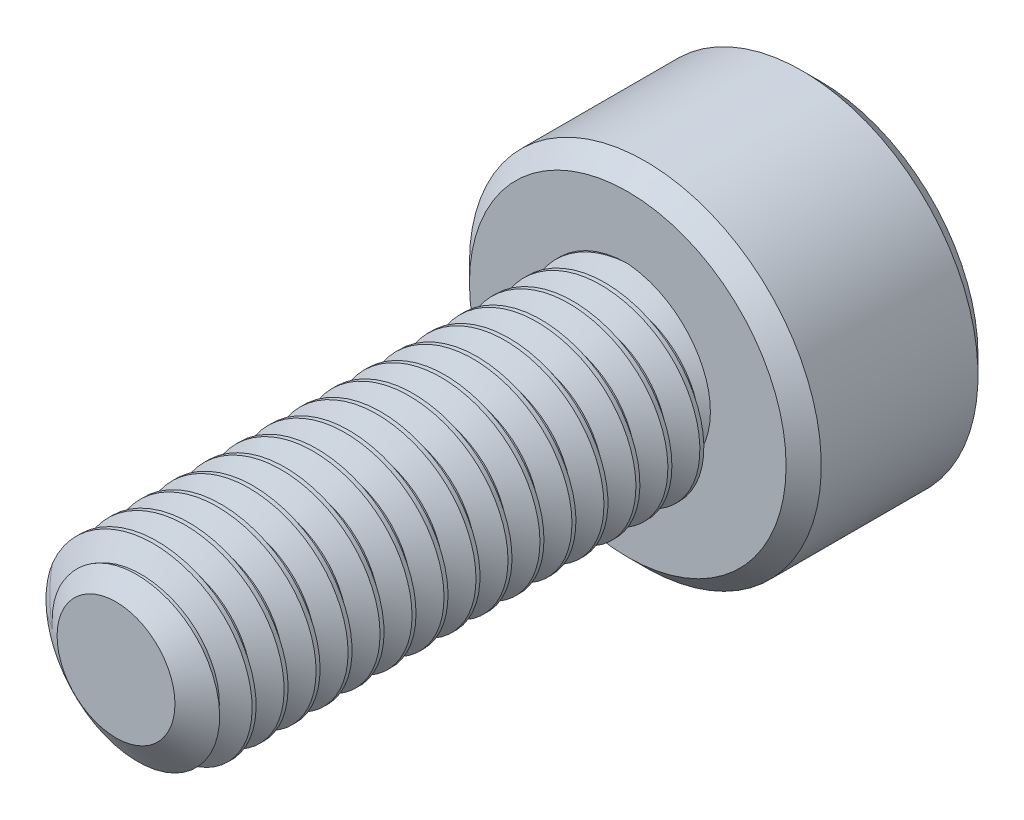
SolidWorks part; units mm, degrees
other "DetailItem1"
ref_plane "Front Plane" through (0, 0, 0) normal (0, 0, 1) x (1, 0, 0)
ref_plane "Top Plane" through (0, 0, 0) normal (0, 1, 0) x (1, 0, 0)
ref_plane "Right Plane" through (0, 0, 0) normal (1, 0, 0) x (0, 0, -1)
sketch "Sketch1" plane through (0, 0, 0) normal (0, 0, 1) x (1, 0, 0)
  circle A0 centre (0, 0) radius 1.5
  dimension "OD" = 3
extrude "Extrude1" add sketch "Sketch1" against normal blind 8
sketch "Sketch2" plane through (0, 0, 0) normal (0, 0, 1) x (1, 0, 0)
  circle A0 centre (0, 0) radius 1.5 construction
  circle A1 centre (0, 0) radius 1.5
curve "Helix/Spiral1" pitch 0.5 height 8.5 radius 1.5 centre (0, 0, 0) axis (0, 0, -1) start towards (0, 1, 0) parameters "pitch"=0.5
sketch "Sketch3" plane through (0, 0, 0) normal (1, 0, 0) x (0, 0, -1)
  line L0 (-0.4375, 1.5) -> (-0.25, 1.1752)
  line L1 (-0.25, 1.1752) -> (-0.1875, 1.1752)
  line L2 (-0.1875, 1.1752) -> (0, 1.5)
  line L3 (-0.4375, 1.5) -> (0, 1.5)
  line L4 (-0.2188, 1.5) -> (-0.2188, 1.1752) construction
  line L5 (-0.3438, 1.3376) -> (-0.0938, 1.3376) construction
  line L6 (0, 1.5) -> (0, -1.5) construction
  dimension "D1" = 0.0625
  dimension "D2" = 0.25
  dimension "D3" = 60
sweep "Cut-Sweep1" cut profiles "Sketch3" path "Helix/Spiral1" align with end faces yes
sketch "Sketch4" plane through (0, 0, 0) normal (1, 0, 0) x (0, 0, -1)
  line L0 (0.4053, 1.5) -> (0, 0.9212)
  line L1 (0, 0.9212) -> (0, 1.5)
  line L2 (0.4053, 1.5) -> (0, 1.5)
  line L3 (-0.4375, 1.5) -> (0, 1.5) construction
  line L4 (0, 0) -> (7.0209, 0) construction
  dimension "D1" = 55
  dimension "D2" = 0.254
revolve "Cut-Revolve1" cut sketch "Sketch4" angle 360 about L4
sketch "Sketch6" plane through (0, 0, -8) normal (0, 0, -1) x (-1, 0, 0)
  circle A0 centre (0, 0) radius 2.75
  dimension "head dia" = 5.5
extrude "Extrude2" add sketch "Sketch6" along normal blind 3
sketch "Sketch7" plane through (0, 0, -11) normal (0, 0, -1) x (-1, 0, 0)
  line L1 (0, 1.4434) -> (-1.25, 0.7217)
  line L2 (-1.25, 0.7217) -> (-1.25, -0.7217)
  line L3 (-1.25, -0.7217) -> (0, -1.4434)
  line L4 (0, -1.4434) -> (1.25, -0.7217)
  line L5 (1.25, -0.7217) -> (1.25, 0.7217)
  line L6 (1.25, 0.7217) -> (0, 1.4434)
  circle A0 centre (0, 0) radius 1.25 construction
  dimension "hex dia" = 2.5
extrude "Cut-Extrude1" cut sketch "Sketch7" against normal blind 1.875
sketch "Sketch8" plane through (0, 0, -11) normal (0, 0, -1) x (-1, 0, 0)
  circle A0 centre (0, 0) radius 1.4434
extrude "Cut-Extrude2" cut sketch "Sketch8" against normal through all draft 45
chamfer "Chamfer1" distance 0.275 angle 45 2 edges at (-2.75, 0, -11) (-2.75, 0, -8)
sketch "Sketch10" plane through (0, 0, -8) normal (0, 0, 1) x (1, 0, 0)
  circle A1 centre (0, 0) radius 1.5
  circle A2 centre (0, 0) radius 1.5
  dimension "D1" = 0
ref_plane "Plane1" through (0, 0, 0) normal (0, 0, 1) x (1, 0, 0)
extrude "partial thread" [suppressed] add sketch "Sketch10" along normal up to surface (36 mm away) separate body up to plane "Plane1"
chamfer "Chamfer2" [suppressed] distance 0.06 angle 45
combine bodies "Combine1" [suppressed] operation type add bodies to combine 107 108
sketch "Sketch9" plane through (0, 0, 0) normal (1, 0, 0) x (0, 0, -1)
  line L0 (0, 1.5) -> (0, -1.5) construction
  line L1 (1.25, 1.5) -> (1.25, -1.5) construction
  dimension "D1" = 1.25
equation "\"D3@Helix/Spiral1\" = \"screw length@Extrude1\"+\"pitch@Helix/Spiral1\""
equation "\"D1@Sketch3\" = \"pitch@Helix/Spiral1\"*.125"
equation "\"D2@Sketch3\" = \"pitch@Helix/Spiral1\"*.5"
equation "\"D1@Cut-Extrude1\" = \"hex dia@Sketch7\"*.75"
equation "\"D1@Chamfer1\" = \"head dia@Sketch6\"*.05"
equation "\"D1@Sketch9\" = \"pitch@Helix/Spiral1\"*2.5"
equation "\"D1@Chamfer2\"=\"OD@Sketch1\"*.02"
